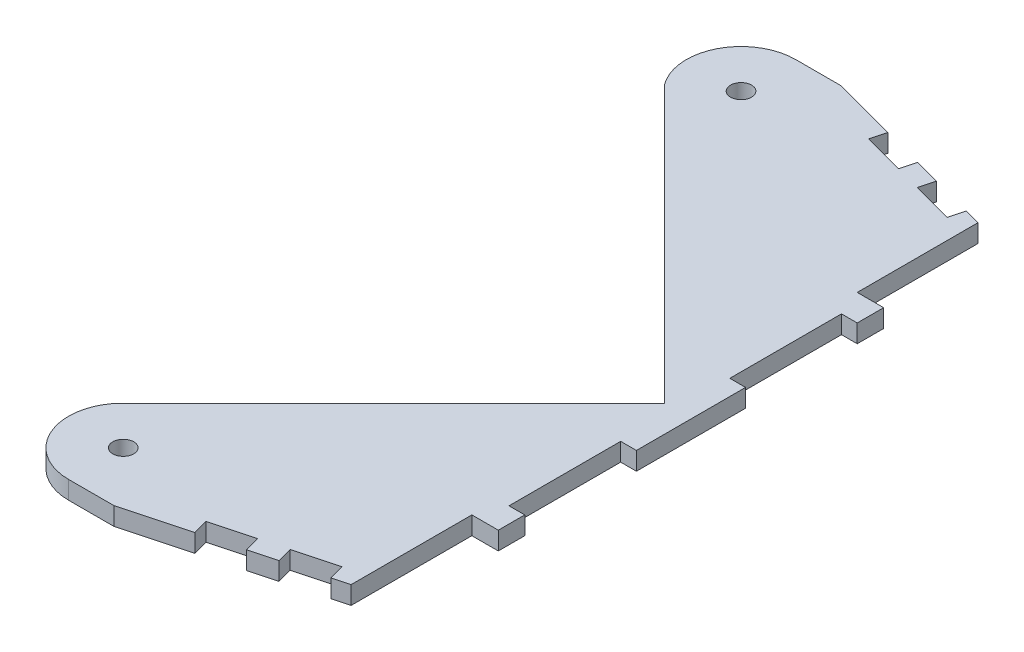
SolidWorks part; units mm, degrees
ref_plane "Front" through (0, 0, 0) normal (0, 0, 1) x (1, 0, 0)
ref_plane "Top" through (0, 0, 0) normal (0, 1, 0) x (1, 0, 0)
ref_plane "Right" through (0, 0, 0) normal (1, 0, 0) x (0, 0, -1)
ref_axis "side-side" through (80.9, 0, 0) along (-1, 0, 0)
ref_axis "up-down" through (0, 50, 0) along (0, -1, 0)
ref_axis "front-back" through (0, 0, -80.9) along (0, 0, 1)
sketch "Sketch1" plane through (0, 0, 0) normal (0, 1, 0) x (1, 0, 0)
  line L1 (0, 0) -> (-83.6295, 83.6295)
  line L3 (0, -94.8336) -> (-56.6019, -110)
  line L4 (-56.6019, 110) -> (0, 94.8336)
  line L5 (-70.3102, 110) -> (-56.6019, 110)
  line L6 (8, 58.293) -> (8, -58.293)
  line L7 (0, 0) -> (58.8362, 0) construction
  line L8 (-70.3102, -110) -> (-56.6019, -110)
  line L10 (0, 0) -> (-83.6295, -83.6295)
  line L12 (0, 94.8336) -> (0, 58.293)
  line L13 (0, 58.293) -> (8, 58.293)
  line L16 (0, -94.8336) -> (0, -58.293)
  line L17 (0, -58.293) -> (8, -58.293)
  circle A0 centre (-70.3102, 93.4511) radius 3.175
  circle A1 centre (-70.3102, -93.4511) radius 3.175
  arc A2 (-83.6295, 83.6295) -> (-70.3102, 110) centre (-70.3102, 93.4511) cw
  arc A3 (-83.6295, -83.6295) -> (-70.3102, -110) centre (-70.3102, -93.4511) ccw
  dimension "D5" = 6.35
  dimension "D1" = 64.6019
  dimension "D2" = 110
  dimension "D3" = 8
  dimension "D4" = 45
  dimension "D6" = 75
  dimension "D7" = 116.586
  dimension "D8" = 8
extrude "Boss-Extrude1" add sketch "Sketch1" along normal blind 5.461
chamfer "Chamfer1" [suppressed] distance 10 distance2 10
sketch "Sketch3" plane through (0, 0, 0) normal (0, 1, 0) x (1, 0, 0)
  line L0 (-37.2834, 104.8236) -> (-24.9202, 101.5109)
  line L1 (-37.2834, 104.8236) -> (-38.5161, 100.2234)
  line L2 (-24.9202, 101.5109) -> (-26.1529, 96.9107)
  line L3 (-38.5161, 100.2234) -> (-26.1529, 96.9107)
  line L4 (-17.1928, 99.4404) -> (-4.8296, 96.1276)
  line L5 (-17.1928, 99.4404) -> (-18.4255, 94.8401)
  line L6 (-4.8296, 96.1276) -> (-6.0623, 91.5274)
  line L7 (-18.4255, 94.8401) -> (-6.0623, 91.5274)
  line L8 (-56.6019, 110) -> (0, 94.8336) construction
  line L9 (-6.1395, 91.5481) -> (-38.4388, 100.2027) construction
  line L10 (0, 0) -> (58.8362, 0) construction
  line L11 (0, 0) -> (58.8362, 0) construction
  line L12 (-18.4255, -94.8401) -> (-6.0623, -91.5274)
  line L13 (-4.8296, -96.1276) -> (-6.0623, -91.5274)
  line L14 (-17.1928, -99.4404) -> (-18.4255, -94.8401)
  line L15 (-17.1928, -99.4404) -> (-4.8296, -96.1276)
  line L16 (-38.5161, -100.2234) -> (-26.1529, -96.9107)
  line L17 (-24.9202, -101.5109) -> (-26.1529, -96.9107)
  line L18 (-37.2834, -104.8236) -> (-38.5161, -100.2234)
  line L19 (-37.2834, -104.8236) -> (-24.9202, -101.5109)
  line L20 (3.2375, 53.213) -> (3.2375, -53.213) construction
  line L21 (8, 50.293) -> (3.2375, 50.293)
  line L22 (8, 50.293) -> (8, 16.51)
  line L23 (8, 16.51) -> (3.2375, 16.51)
  line L24 (3.2375, 50.293) -> (3.2375, 16.51)
  line L25 (3.2375, -50.293) -> (3.2375, -16.51)
  line L26 (8, -16.51) -> (3.2375, -16.51)
  line L27 (8, -50.293) -> (8, -16.51)
  line L28 (8, -50.293) -> (3.2375, -50.293)
  line L29 (8, 58.293) -> (0, 58.293) construction
  dimension "D1" = 8
extrude "Cut-Extrude2" cut sketch "Sketch3" along normal blind 10
